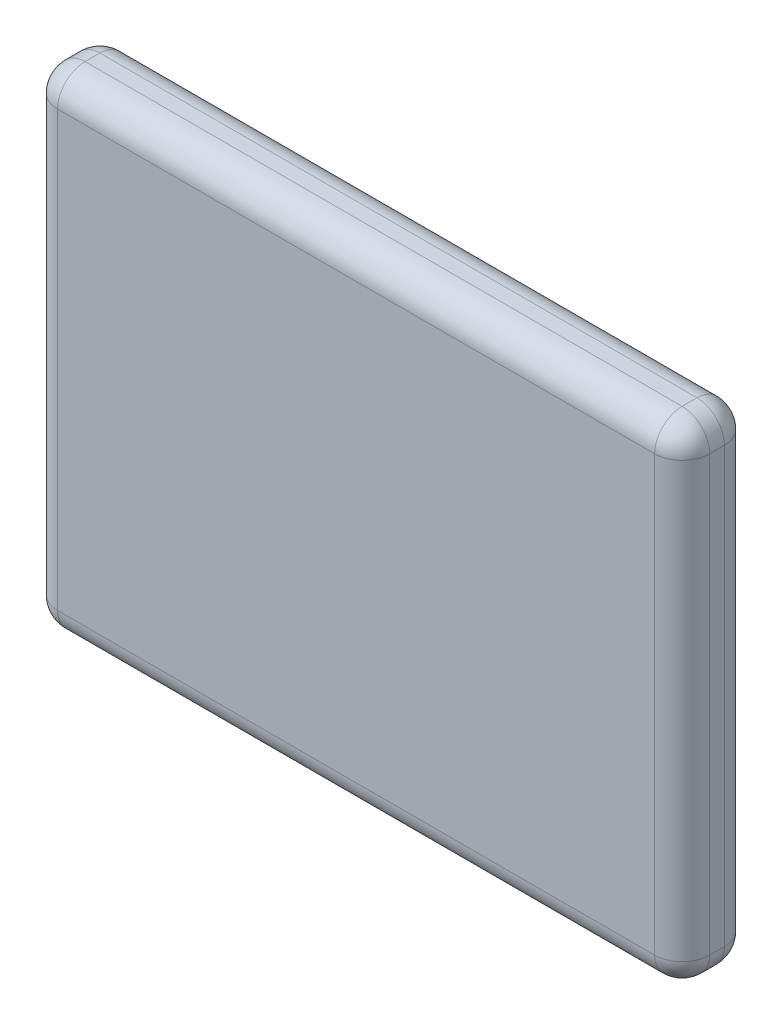
SolidWorks part; units mm, degrees
material "Custom Plastic"
ref_plane "Front Plane" through (0, 0, 0) normal (0, 0, 1) x (1, 0, 0)
ref_plane "Top Plane" through (0, 0, 0) normal (0, 1, 0) x (1, 0, 0)
ref_plane "Right Plane" through (0, 0, 0) normal (1, 0, 0) x (0, 0, -1)
sketch "Sketch1" plane through (0, 0, 0) normal (0, 0, 1) x (1, 0, 0)
  line L1 (-288.8383, 70.5581) -> (186.1617, 70.5581)
  line L2 (-288.8383, 70.5581) -> (-288.8383, -285.7819)
  line L3 (-288.8383, -285.7819) -> (186.1617, -285.7819)
  line L4 (186.1617, 70.5581) -> (186.1617, -285.7819)
  dimension "D1" = 475
  dimension "D2" = 356.34
extrude "Boss-Extrude1" add sketch "Sketch1" along normal blind 50.8
fillet "Fillet2" radius 20 4 edges at (-288.8383, -107.6119, 50.8) (-51.3383, -285.7819, 50.8) (186.1617, -107.6119, 50.8) (-51.3383, 70.5581, 50.8)
fillet "Fillet6" radius 20 8 edges at (186.1617, 70.5581, 15.4) (186.1617, -285.7819, 15.4) (-282.9804, -279.924, 44.9421) (-282.9804, 64.7002, 44.9421) (180.3039, 64.7002, 44.9421) (180.3039, -279.924, 44.9421) (-288.8383, -285.7819, 15.4) (-288.8383, 70.5581, 15.4)
fillet "Fillet7" radius 20 8 edges at (180.3039, 64.7002, 0) (186.1617, -107.6119, 0) (180.3039, -279.924, 0) (-51.3383, -285.7819, 0) (-282.9804, -279.924, 0) (-288.8383, -107.6119, 0) (-282.9804, 64.7002, 0) (-51.3383, 70.5581, 0)
